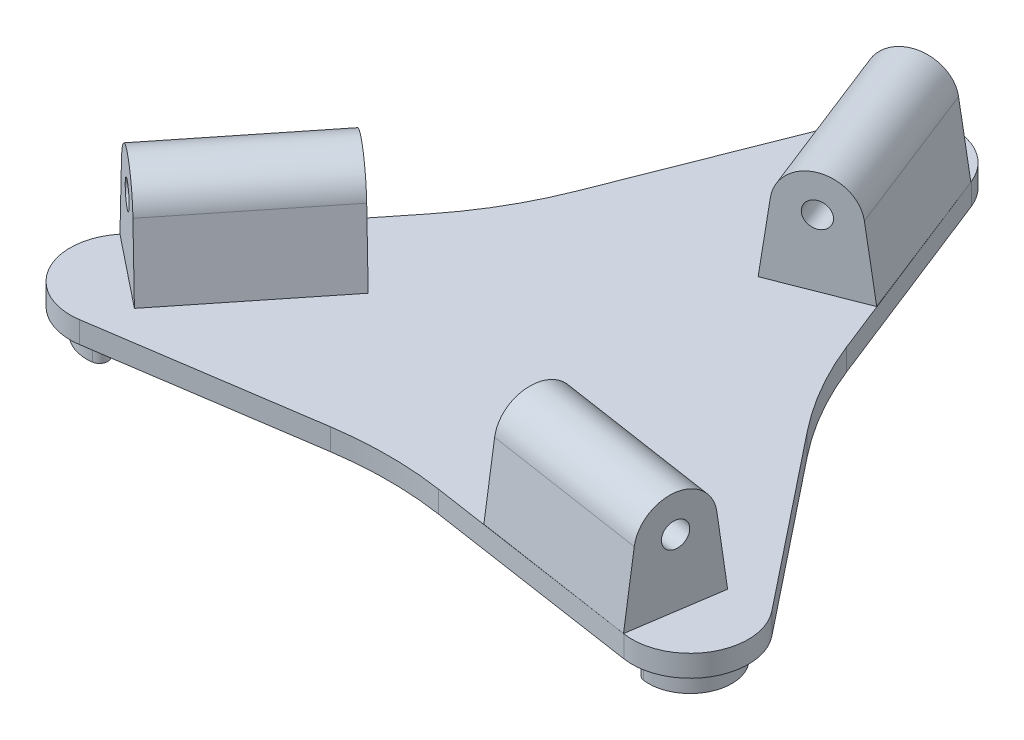
SolidWorks part; units mm, degrees
ref_plane "Front Plane" through (0, 0, 0) normal (0, 0, 1) x (1, 0, 0)
ref_plane "Top Plane" through (0, 0, 0) normal (0, 1, 0) x (1, 0, 0)
ref_plane "Right Plane" through (0, 0, 0) normal (1, 0, 0) x (0, 0, -1)
sketch "Sketch1" plane through (0, 0, 0) normal (0, 1, 0) x (1, 0, 0)
  line L0 (0, 0) -> (-68.3868, -39.4831) construction
  line L1 (0, 0) -> (0, 74.7926) construction
  line L2 (0, 0) -> (79.4724, -45.8834) construction
  line L3 (-6.5, 41.5729) -> (-16.2217, 16.8712)
  line L4 (6.5, 41.5729) -> (16.2217, 16.8712)
  line L5 (39.2532, -15.1573) -> (22.7217, 5.6128)
  line L6 (32.7532, -26.4156) -> (6.5, -22.484)
  line L7 (-32.7532, -26.4156) -> (-6.5, -22.484)
  line L8 (-39.2532, -15.1573) -> (-22.7217, 5.6128)
  arc A1 (-6.5, 41.5729) -> (6.5, 41.5729) centre (0, 39.0147) cw
  arc A2 (-16.2217, 16.8712) -> (-19.0526, 11) centre (-57.0604, 32.9438) cw
  arc A3 (16.2217, 16.8712) -> (19.0526, 11) centre (57.0604, 32.9438) ccw
  arc A4 (39.2532, -15.1573) -> (32.7532, -26.4156) centre (33.7877, -19.5074) cw
  arc A5 (22.7217, 5.6128) -> (19.0526, 11) centre (57.0604, 32.9438) cw
  arc A6 (6.5, -22.484) -> (0, -22) centre (0, -65.8877) ccw
  arc A7 (-32.7532, -26.4156) -> (-39.2532, -15.1573) centre (-33.7877, -19.5074) cw
  arc A8 (-6.5, -22.484) -> (0, -22) centre (0, -65.8877) cw
  arc A9 (-22.7217, 5.6128) -> (-19.0526, 11) centre (-57.0604, 32.9438) ccw
  dimension "D3" = 22
  dimension "D6" = 6.9853
  dimension "D4" = 39.0147
  dimension "D1" = 60
  dimension "D2" = 60
  dimension "D5" = 6.5
  dimension "D7" = 6.5
extrude "Extrude2" add sketch "Sketch1" along normal blind 2.6
sketch "Sketch2" plane through (0, 0, 0) normal (0, 1, 0) x (1, 0, 0)
  line L1 (173205.0808, 100000) -> (-173273.4675, -100039.4831) construction
  line L2 (-22.7213, -13.1182) -> (-42.235, -24.3844) construction
  arc A0 (-33.1351, -24.4646) -> (-37.7545, -16.4635) centre (-33.7877, -19.5074) cw
  arc A1 (-33.3962, -22.4817) -> (-36.1678, -17.6811) centre (-33.7877, -19.5074) cw
  arc A2 (-37.7545, -16.4635) -> (-36.1678, -17.6811) centre (-36.9611, -17.0723) cw
  arc A3 (-33.1351, -24.4646) -> (-33.3962, -22.4817) centre (-33.2656, -23.4731) ccw
  arc A4 (-4.6194, 40.9281) -> (4.6194, 40.9281) centre (0, 39.0147) cw
  arc A5 (-2.7716, 40.1628) -> (2.7716, 40.1628) centre (0, 39.0147) cw
  arc A6 (4.6194, 40.9281) -> (2.7716, 40.1628) centre (3.6955, 40.5454) cw
  arc A7 (-4.6194, 40.9281) -> (-2.7716, 40.1628) centre (-3.6955, 40.5454) ccw
  arc A8 (37.7545, -16.4635) -> (33.1351, -24.4646) centre (33.7877, -19.5074) cw
  arc A9 (36.1678, -17.6811) -> (33.3962, -22.4817) centre (33.7877, -19.5074) cw
  arc A10 (33.1351, -24.4646) -> (33.3962, -22.4817) centre (33.2656, -23.4731) cw
  arc A11 (37.7545, -16.4635) -> (36.1678, -17.6811) centre (36.9611, -17.0723) ccw
  dimension "D1" = 1
  dimension "D3" = 135
  dimension "D2" = 5
extrude "Extrude3" add sketch "Sketch2" against normal blind 3
sketch "Sketch3" plane through (0, 0, 0) normal (0, 1, 0) x (1, 0, 0)
  line L0 (6.5343, 41.4858) -> (13.8348, 22.8659)
  line L1 (3.5938, 18.8506) -> (0, 0) construction
  line L2 (13.8348, 22.8659) -> (3.5938, 18.8506)
  line L3 (3.5938, 18.8506) -> (-3.7067, 37.4705)
  line L4 (-3.7067, 37.4705) -> (6.5343, 41.4858)
  line L5 (32.6606, -26.4017) -> (12.885, -23.4142)
  line L6 (12.885, -23.4142) -> (14.5282, -12.5376)
  line L7 (14.5282, -12.5376) -> (34.3038, -15.5252)
  line L8 (34.3038, -15.5252) -> (32.6606, -26.4017)
  line L9 (-39.1949, -15.0841) -> (-26.7198, 0.5483)
  line L10 (-26.7198, 0.5483) -> (-18.122, -6.313)
  line L11 (-18.122, -6.313) -> (-30.5971, -21.9454)
  line L12 (-30.5971, -21.9454) -> (-39.1949, -15.0841)
  line L13 (0, 0) -> (-18.122, -6.313) construction
  line L14 (0, 0) -> (14.5282, -12.5376) construction
  line L15 (6.5, 41.5729) -> (16.2217, 16.8712) construction
  dimension "D1" = 20
  dimension "D2" = 11
  dimension "D3" = 73.5
  dimension "D4" = 64.9
extrude "Extrude4" add sketch "Sketch3" along normal blind 15
ref_plane "Plane2" through (-13.2278, 0, -33.7375) normal (-0.365, 0, -0.931) x (-0.931, 0, 0.365)
sketch "Sketch4" plane through (-13.2278, 0, -33.7375) normal (-0.365, 0, -0.931) x (-0.931, 0, 0.365)
  line L0 (-21.2268, 2.6) -> (-20.0885, 11.1787)
  line L1 (-15.7268, 15) -> (-15.7268, 2.6) construction
  line L3 (-21.2268, 2.6) -> (-10.2268, 2.6) construction
  line L4 (-21.2268, 2.6) -> (-22.2268, 2.6)
  line L5 (-10.2268, 2.6) -> (-11.365, 11.1787)
  line L6 (-21.2268, 15) -> (-10.2268, 15) construction
  line L7 (-22.2268, 2.6) -> (-22.2268, 16)
  line L8 (-22.2268, 16) -> (-9.2268, 16)
  line L9 (-9.2268, 16) -> (-9.2268, 2.6)
  line L10 (-9.2268, 2.6) -> (-10.2268, 2.6)
  arc A0 (-20.0885, 11.1787) -> (-11.365, 11.1787) centre (-15.7268, 10.6) cw
  circle A1 centre (-15.7268, 10.6) radius 1.5
  point P5 (-15.7268, 15)
  dimension "D4" = 3
  dimension "D1" = 8
  dimension "D2" = 1
  dimension "D3" = 1
extrude "Cut-Extrude1" cut sketch "Sketch4" against normal blind 30
ref_axis "Axis1" through (0, 36.0062, 0) along (0, -1, 0)
pattern_circular "CirPattern1" count 3 every 120 about axis through (0, 36.0062, 0) along (0, -1, 0) of "Cut-Extrude1"
